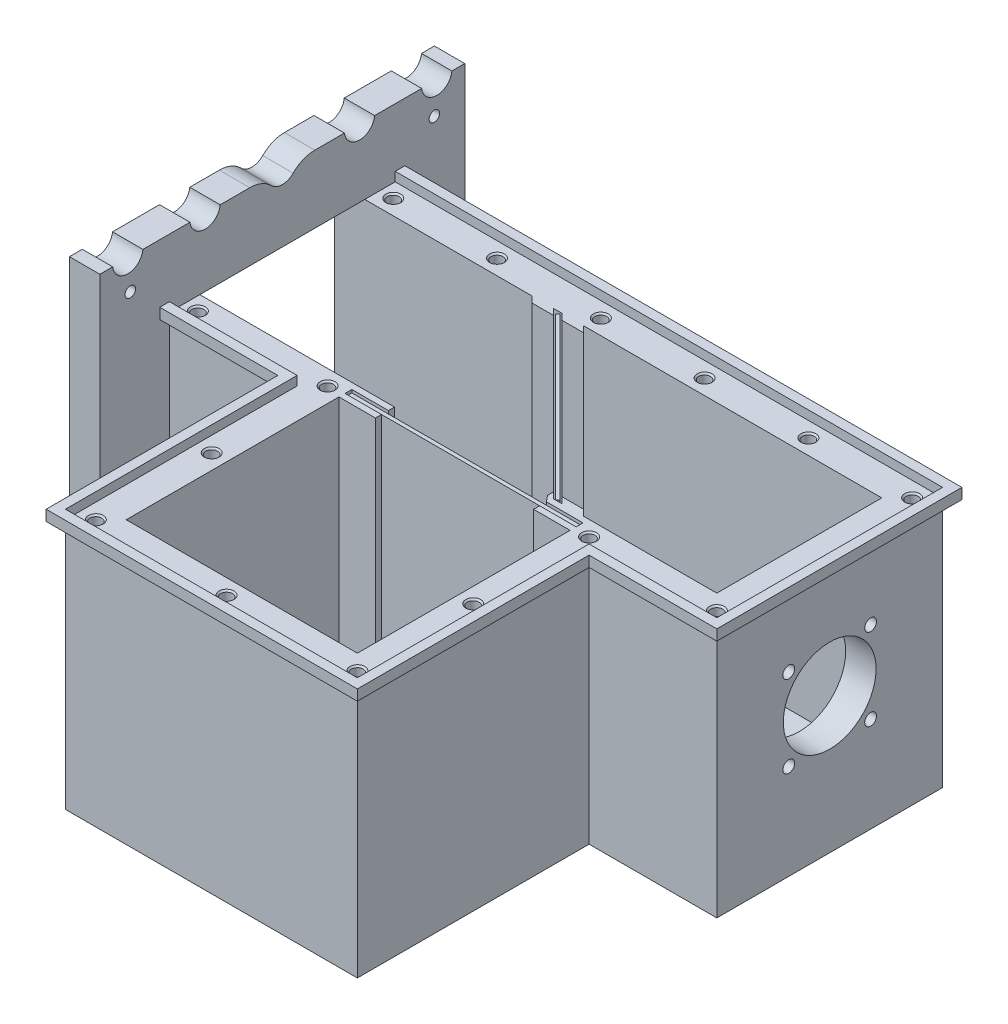
SolidWorks part; units mm, degrees
note: The reader was unsure of these and kept them because the rebuilt part matched: shared geometry of "Sketch1<5>", "Sketch1<6>", "Outline Sketch<10>".
ref_plane "Front Plane" through (0, 0, 0) normal (0, 0, 1) x (1, 0, 0)
ref_plane "Top Plane" through (0, 0, 0) normal (0, 1, 0) x (1, 0, 0)
ref_plane "Right Plane" through (0, 0, 0) normal (1, 0, 0) x (0, 0, -1)
sketch "Outline Sketch" plane through (0, 0, 0) normal (0, 1, 0) x (1, 0, 0)
  line L0 (78.4332, -3.5355) -> (81.9688, 0)
  line L1 (0, 0) -> (180, 0)
  line L2 (0, 0) -> (0, -54.2401)
  line L3 (0, -54.2401) -> (180, -54.2401)
  line L4 (180, 0) -> (180, -54.2401)
  line L9 (81.9688, 0) -> (132.6734, -50.7046)
  line L10 (132.6734, -50.7046) -> (129.1378, -54.2401)
  line L11 (129.1378, -54.2401) -> (78.4332, -3.5355)
  line L12 (72.0693, 0) -> (68.5337, -3.5355)
  line L13 (68.5337, -3.5355) -> (119.2383, -54.2401)
  line L14 (119.2383, -54.2401) -> (122.7739, -50.7046)
  line L15 (122.7739, -50.7046) -> (72.0693, 0)
  line L16 (0, 10.3799) -> (0, -64.6201) construction
  line L17 (73.4835, -0.7071) -> (126.5165, -53.7401) construction
  line L18 (126.5165, -53.7401) -> (127.2236, -53.033) construction
  line L19 (127.2236, -53.033) -> (74.1906, 0) construction
  line L20 (74.1906, 0) -> (73.4835, -0.7071) construction
  line L21 (78.0797, -3.8891) -> (78.4332, -3.5355) construction
  line L22 (77.3726, -4.5962) -> (77.019, -4.9497) construction
  line L23 (100, -27.2236) -> (100, -54.2401) construction
  line L24 (62, -54.2401) -> (138, -54.2401)
  line L25 (62, -54.2401) -> (62, -130.4401)
  line L26 (62, -130.4401) -> (138, -130.4401)
  line L27 (138, -54.2401) -> (138, -130.4401)
  line L36 (62, -58.4901) -> (74, -58.4901)
  line L37 (62, -58.4901) -> (62, -60.4901)
  line L38 (62, -60.4901) -> (74, -60.4901)
  line L39 (74, -58.4901) -> (74, -60.4901)
  line L40 (138, -58.4901) -> (126, -58.4901)
  line L41 (138, -58.4901) -> (138, -60.4901)
  line L42 (138, -60.4901) -> (126, -60.4901)
  line L43 (126, -58.4901) -> (126, -60.4901)
  line L48 (137.5, -56.2401) -> (137.5, -56.7401) construction
  line L49 (62.5, -56.7401) -> (137.5, -56.7401) construction
  line L50 (62.5, -56.7401) -> (62.5, -57.9901) construction
  line L51 (62.5, -57.9901) -> (137.5, -57.9901) construction
  line L52 (137.5, -56.7401) -> (137.5, -57.9901) construction
  line L53 (137.5, -57.9901) -> (137.5, -58.4901) construction
  line L54 (137.5, -56.7401) -> (138, -56.7401) construction
  line L55 (62.5, -56.7401) -> (62, -56.7401) construction
  line L56 (0, 22.8799) -> (0, -77.1201) construction
  line L57 (10, 10) -> (190, 10)
  line L58 (0, 27.8799) -> (10, 27.8799)
  line L59 (0, 27.8799) -> (0, 0)
  line L60 (0, 0) -> (10, 0)
  line L61 (10, 27.8799) -> (10, 0)
  line L62 (0, -54.2401) -> (10, -54.2401)
  line L63 (0, -54.2401) -> (0, -82.1201)
  line L64 (0, -82.1201) -> (10, -82.1201)
  line L65 (10, -54.2401) -> (10, -82.1201)
  line L66 (190, 10) -> (190, -64.2401)
  line L67 (190, -64.2401) -> (148, -64.2401)
  line L68 (148, -64.2401) -> (148, -140.4401)
  line L69 (148, -140.4401) -> (52, -140.4401)
  line L70 (52, -140.4401) -> (52, -64.2401)
  line L71 (52, -64.2401) -> (10, -64.2401)
  line L72 (180, 0) -> (180, 10) construction
  line L73 (180, 0) -> (190, 0) construction
  line L74 (148, -64.2401) -> (148, -54.2401) construction
  line L75 (138, -130.4401) -> (148, -130.4401) construction
  line L76 (62, -130.4401) -> (62, -140.4401) construction
  line L77 (62, -130.4401) -> (52, -130.4401) construction
  line L78 (52, -64.2401) -> (52, -54.2401) construction
  line L79 (68.5337, -3.5355) -> (68.5337, 0)
  line L80 (126.5165, -53.7401) -> (127.5772, -52.6795)
  line L81 (10, 0) -> (10, -54.2401)
  line L82 (10, 5) -> (190, 5) construction
  line L83 (185, 10) -> (185, -64.2401) construction
  line L84 (190, -59.2401) -> (138, -59.2401) construction
  line L85 (10, -59.2401) -> (62, -59.2401) construction
  line L86 (57, -54.2401) -> (57, -140.4401) construction
  line L87 (52, -135.4401) -> (148, -135.4401) construction
  line L88 (143, -54.2401) -> (143, -140.4401) construction
  line L89 (68.5337, -3.5355) -> (64.9982, 0)
  line L90 (190, -11.8701) -> (200, -11.8701) construction
  line L91 (190, -11.8701) -> (190, -42.3701) construction
  line L92 (190, -42.3701) -> (200, -42.3701) construction
  line L93 (200, -11.8701) -> (200, -42.3701) construction
  line L94 (78.4332, -3.5355) -> (74.8977, 0)
  line L95 (74.8977, 0) -> (81.9688, 0)
  line L96 (74.0693, -2) -> (66.9982, -2)
  line L97 (76.8977, -2) -> (83.9688, -2)
  line L98 (132.6734, -50.7046) -> (136.2089, -54.2401)
  line L99 (127.1378, -52.2401) -> (134.2089, -52.2401)
  line L100 (122.7739, -50.7046) -> (126.3094, -54.2401)
  line L101 (126.3094, -54.2401) -> (119.2383, -54.2401)
  line L102 (124.3094, -52.2401) -> (117.2383, -52.2401)
  line L103 (100, -54.2401) -> (100, -57.9901) construction
  line L104 (62, -54.2401) -> (74, -54.2401)
  line L105 (62, -54.2401) -> (62, -56.2401)
  line L106 (62, -56.2401) -> (74, -56.2401)
  line L107 (74, -54.2401) -> (74, -56.2401)
  line L108 (138, -54.2401) -> (126, -54.2401)
  line L109 (138, -54.2401) -> (138, -56.2401)
  line L110 (138, -56.2401) -> (126, -56.2401)
  line L111 (126, -54.2401) -> (126, -56.2401)
  line L112 (124.3094, -52.2401) -> (124.3094, -54.2401)
  line L113 (124.3094, -54.2401) -> (126.3094, -54.2401)
  line L114 (124.3094, -54.2401) -> (126, -56.2401)
  line L115 (180, -54.2401) -> (180, -64.2401) construction
  point P18 (0, -27.1201)
  point P51 (0, -27.1201)
  point P52 (0, -27.1201)
  point P80 (180, 5)
  point P83 (185, 0)
  point P85 (200, -27.1201)
  point P86 (190, -27.1201)
  point P94 (148, -59.2401)
  point P103 (57, -130.4401)
  point P104 (143, -130.4401)
  point P105 (62, -135.4401)
  dimension "D23" = 10
  dimension "D24" = 30.5
  dimension "D25" = 2
  dimension "D26" = 2
  dimension "D1" = 5
  dimension "D2" = 45
  dimension "D3" = 1
  dimension "D4" = 75
  dimension "D5" = 200
  dimension "D6" = 53.7401
  dimension "D7" = 0.5
  dimension "D8" = 75
  dimension "D9" = 1.25
  dimension "D10" = 0.5
  dimension "D11" = 76
  dimension "D12" = 52.3259
  dimension "D13" = 0.5
  dimension "D14" = 2
  dimension "D15" = 100
  dimension "D16" = 76.2
  dimension "D17" = 75
  dimension "D18" = 100
  dimension "D19" = 10
  dimension "D20" = 5
  dimension "D21" = 10
  dimension "D22" = 17.8799
  dimension "D27" = 52
  dimension "D29" = 0.5
extrude "Floor" add sketch "Outline Sketch" along normal blind 7
extrude "Walls" add sketch "Sketch1<5>" along normal blind 75.5 from surface at 7
sketch "Sketch1<5>" plane through (0, 0, 0) normal (0, 1, 0) x (1, 0, 0) same geometry as "Outline Sketch"
extrude "Beam Splitter Supports" add sketch "Sketch1<6>" along normal blind 2 from surface at 7 separate body contours L11 L99 L10 L9 L97 L0 | L99 L10 L3 L98 | L10 L99 L98 | L99 L11 L10 | L102 L14 L15 L96 L12 L13 | L14 L102 L13 | L112 L102 L14 L3 | L102 L100 L14 | L100 L112 L101 | L94 L97 L0 L1 | L0 L97 L9 | L97 L94 L0 | L96 L79 L1 L89 | L79 L96 L89 | L12 L96 L79 | L96 L15 L12 | L96 L12 L1 L79 starting at face at (90, 7, 56.0437)
sketch "Sketch1<6>" plane through (0, 0, 0) normal (0, 1, 0) x (1, 0, 0) same geometry as "Outline Sketch"
extrude "Beam Splitter Vertical Supports" add sketch "Outline Sketch<10>" along normal up to surface (82.5 mm away) contours L96 L15 L12 | L96 L12 L1 L79 | L96 L79 L1 L89 | L94 L97 L0 L1 | L0 L97 L9 | L99 L11 L10 | L99 L10 L3 L98 | L100 L112 L101 | L101 L114 L111 up to face at (99.2857, 82.5, 60.5915)
sketch "Outline Sketch<10>" plane through (0, 0, 0) normal (0, 1, 0) x (1, 0, 0) same geometry as "Outline Sketch"
ref_plane "SM1 Camera Flange Plane" through (190, 0, 0) normal (1, 0, 0) x (0, 0, -1)
sketch "SM1 Flange Sketch" plane through (190, 0, 0) normal (1, 0, 0) x (0, 0, -1)
  line L0 (-54.2401, 82.5) -> (0, 82.5) construction
  line L1 (-40.5821, 58.212) -> (-13.6581, 58.212) construction
  line L2 (-40.5821, 58.212) -> (-40.5821, 31.288) construction
  line L3 (-40.5821, 31.288) -> (-13.6581, 31.288) construction
  line L4 (-13.6581, 58.212) -> (-13.6581, 31.288) construction
  line L6 (-64.2401, 9) -> (10, 9) construction
  line L7 (-64.2401, 82.5) -> (-64.2401, 0) construction
  line L8 (10, 82.5) -> (10, 0) construction
  line L10 (22.8799, 0) -> (-77.1201, 0) construction
  line L11 (-64.2401, 82.5) -> (10, 82.5) construction
  line L12 (-64.2401, 7) -> (10, 7) construction
  line L14 (-64.2401, 82.5) -> (-64.2401, 0) construction
  line L15 (-64.2401, 82) -> (10, 82) construction
  line L16 (10, 80.5) -> (-64.2401, 80.5) construction
  circle A0 centre (-27.1201, 44.75) radius 15.25
  circle A1 centre (-40.5821, 58.212) radius 1.945
  circle A2 centre (-13.6581, 58.212) radius 1.945
  circle A3 centre (-13.6581, 31.288) radius 1.945
  circle A4 centre (-40.5821, 31.288) radius 1.945
  point P13 (-27.1201, 58.212)
  point P14 (-13.6581, 44.75)
  point P17 (-27.1201, 82.5)
  dimension "D2" = 30.5
  dimension "D1" = 26.924
  dimension "D7" = 75
  dimension "D4" = 35.75
extrude "SM1 Flange Cutout" cut sketch "SM1 Flange Sketch" against normal up to surface (10 mm away) up to face at (180, 44.75, 27.1201)
sketch "BS & Diffuser Example Sketch" plane through (0, 0, 0) normal (0, 1, 0) x (1, 0, 0)
  line L0 (73.4835, -0.7071) -> (126.5165, -53.7401)
  line L1 (126.5165, -53.7401) -> (127.2236, -53.033)
  line L2 (127.2236, -53.033) -> (74.1906, 0)
  line L3 (74.1906, 0) -> (73.4835, -0.7071)
  line L4 (62.5, -56.7401) -> (62.5, -57.9901)
  line L5 (62.5, -57.9901) -> (137.5, -57.9901)
  line L6 (137.5, -57.9901) -> (137.5, -56.7401)
  line L7 (137.5, -56.7401) -> (62.5, -56.7401)
extrude "BS & Diffuser Example Planes" add sketch "BS & Diffuser Example Sketch" along normal blind 75 from surface at 7 separate body contours L6 L7 L4 L5 | L2 L3 L0 L1 starting at face at (81.9339, 7, 56.0437)
ref_plane "Cryostat Flange Plane" through (10, 0, 0) normal (-1, 0, 0) x (0, 0, 1)
sketch "Cryostat Flange Sketch" plane through (10, 0, 0) normal (-1, 0, 0) x (0, 0, 1)
  line L0 (-23.6799, 105.2669) -> (1.7201, 105.2669) construction
  line L1 (-32.8799, 104.75) -> (87.1201, 104.75)
  line L2 (-32.8799, 104.75) -> (-32.8799, -15.25)
  line L3 (-32.8799, -15.25) -> (87.1201, -15.25)
  line L4 (87.1201, 104.75) -> (87.1201, -15.25)
  line L5 (-22.8799, 94.75) -> (77.1201, 94.75) construction
  line L6 (-22.8799, 94.75) -> (-22.8799, -5.25) construction
  line L7 (-22.8799, -5.25) -> (77.1201, -5.25) construction
  line L8 (77.1201, 94.75) -> (77.1201, -5.25) construction
  line L9 (-10.3799, 82.25) -> (64.6201, 82.25) construction
  line L10 (-10.3799, 82.25) -> (-10.3799, 7.25) construction
  line L11 (-10.3799, 7.25) -> (64.6201, 7.25) construction
  line L12 (64.6201, 82.25) -> (64.6201, 7.25) construction
  line L13 (0, 7) -> (54.2401, 7)
  line L14 (0, 7) -> (0, 82.5)
  line L15 (0, 82.5) -> (54.2401, 82.5)
  line L16 (54.2401, 7) -> (54.2401, 82.5)
  line L17 (1.7201, 105.2669) -> (27.1201, 105.2669) construction
  line L18 (27.1201, 105.2669) -> (52.5201, 105.2669) construction
  line L19 (52.5201, 105.2669) -> (77.9201, 105.2669) construction
  circle A0 centre (-22.8799, 94.75) radius 1.725
  circle A1 centre (77.1201, 94.75) radius 1.725
  circle A2 centre (77.1201, -5.25) radius 1.725
  circle A3 centre (-22.8799, -5.25) radius 1.725
  circle A4 centre (27.1201, 44.75) radius 0.5 construction
  circle A5 centre (27.1201, 44.75) radius 15.25 construction
  circle A6 centre (-23.6799, 105.2669) radius 5
  circle A7 centre (1.7201, 105.2669) radius 5
  circle A8 centre (27.1201, 105.2669) radius 5
  circle A9 centre (52.5201, 105.2669) radius 5
  circle A10 centre (77.9201, 105.2669) radius 5
  point P12 (27.1201, 104.75)
  point P13 (-32.8799, 44.75)
  point P14 (27.1201, 82.25)
  point P17 (-10.3799, 44.75)
  point P42 (0, 0)
  point P43 (27.1201, 109.7584)
  point P44 (27.1201, 106.4508)
  dimension "D3" = 3.45
  dimension "D7" = 1
  dimension "D10" = 10
  dimension "D1" = 120
  dimension "D2" = 100
  dimension "D4" = 10
  dimension "D5" = 10
  dimension "D6" = 75
  dimension "D8" = 25.4
  dimension "D11" = 0.5169
extrude "Crystat Flange Extrusion " add sketch "Cryostat Flange Sketch" along normal blind 10 contours A10 L1 A9 A8 A7 A6 L2 L3 L4 A3 A2 A1 A0 L16 L13 L14 L15
ref_plane "Threaded Inserts" through (0, 82.5, 0) normal (0, 1, 0) x (1, 0, 0)
sketch "Threaded Insert Sketch" plane through (0, 82.5, 0) normal (0, 1, 0) x (1, 0, 0)
  line L0 (10, 5) -> (190, 5) construction
  line L1 (10, 27.8799) -> (10, 0) construction
  line L2 (10, -59.2401) -> (62, -59.2401) construction
  line L3 (190, -59.2401) -> (138, -59.2401) construction
  line L4 (143, -54.2401) -> (143, -140.4401) construction
  line L5 (185, 10) -> (185, -64.2401) construction
  line L6 (57, -54.2401) -> (57, -140.4401) construction
  line L7 (52, -135.4401) -> (148, -135.4401) construction
  circle A0 centre (14.3688, 5) radius 1.9431
  circle A1 centre (14.3688, 5) radius 4.3688 construction
  circle A2 centre (48.495, 5) radius 1.9431
  circle A3 centre (48.495, 5) radius 4.3688 construction
  circle A4 centre (82.6213, 5) radius 1.9431
  circle A5 centre (82.6213, 5) radius 4.3688 construction
  circle A6 centre (116.7475, 5) radius 1.9431
  circle A7 centre (116.7475, 5) radius 4.3688 construction
  circle A8 centre (150.8738, 5) radius 1.9431
  circle A9 centre (150.8738, 5) radius 4.3688 construction
  circle A10 centre (185, 5) radius 1.9431
  circle A11 centre (185, 5) radius 4.3688 construction
  circle A12 centre (14.3688, -59.2401) radius 1.9431
  circle A13 centre (14.3688, -59.2401) radius 4.3688 construction
  circle A14 centre (57, -59.2401) radius 1.9431
  circle A15 centre (57, -59.2401) radius 4.3688 construction
  circle A16 centre (185, -59.2401) radius 1.9431
  circle A17 centre (185, -59.2401) radius 4.3688 construction
  circle A18 centre (143, -59.2401) radius 1.9431
  circle A19 centre (143, -59.2401) radius 4.3688 construction
  circle A20 centre (57, -135.4401) radius 1.9431
  circle A21 centre (57, -135.4401) radius 4.3688 construction
  circle A22 centre (143, -135.4401) radius 1.9431
  circle A23 centre (143, -135.4401) radius 4.3688 construction
  circle A24 centre (57, -97.3401) radius 1.9431
  circle A25 centre (57, -97.3401) radius 4.3688 construction
  circle A26 centre (143, -97.3401) radius 1.9431
  circle A27 centre (143, -97.3401) radius 4.3688 construction
  circle A28 centre (100, -135.4401) radius 1.9431
  circle A29 centre (100, -135.4401) radius 4.3688 construction
  dimension "D1" = 3.8862
  dimension "D2" = 8.7376
  dimension "D4" = 34.1262
  dimension "D3" = 6
extrude "Cut-Extrude2" cut sketch "Threaded Insert Sketch" against normal blind 10 contours A0 | A2 | A4 | A6 | A10 | A8 | A16 | A18 | A26 | A28 | A22 | A20 | A24 | A14 | A12
chamfer "Chamfer1" distance 0.5 angle 45 15 edges at (14.3688, 82.5, -3.0569) (14.3688, 82.5, 61.1832) (57, 82.5, 137.3832) (100, 82.5, 137.3832) (143, 82.5, 137.3832) (57, 82.5, 99.2832) (57, 82.5, 61.1832) (143, 82.5, 99.2832) (143, 82.5, 61.1832) (185, 82.5, 61.1832) (185, 82.5, -3.0569) (116.7475, 82.5, -3.0569) (150.8738, 82.5, -3.0569) (82.6213, 82.5, -3.0569) (48.495, 82.5, -3.0569)
sketch "Sketch7" plane through (0, 82.5, 0) normal (0, 1, 0) x (1, 0, 0)
  line L0 (10, 13.175) -> (193.175, 13.175)
  line L1 (10, 27.8799) -> (10, 0) construction
  line L2 (193.175, 13.175) -> (193.175, -67.4151)
  line L3 (193.175, -67.4151) -> (151.175, -67.4151)
  line L4 (151.175, -67.4151) -> (151.175, -143.6151)
  line L5 (151.175, -143.6151) -> (48.825, -143.6151)
  line L6 (48.825, -143.6151) -> (48.825, -67.4151)
  line L7 (48.825, -67.4151) -> (10, -67.4151)
  line L9 (10, -54.2401) -> (10, -82.1201) construction
  line L10 (190, 10) -> (190, 13.175) construction
  line L11 (190, -81.8967) -> (190, 81.8967) construction
  line L12 (190, 10) -> (193.175, 10) construction
  line L13 (190, -64.2401) -> (193.175, -64.2401) construction
  line L14 (190, -64.2401) -> (190, -67.4151) construction
  line L15 (151.175, -67.4151) -> (151.175, -64.2401) construction
  line L16 (190, -64.2401) -> (148, -64.2401) construction
  line L17 (151.175, -67.4151) -> (148, -67.4151) construction
  line L18 (148, -64.2401) -> (148, -140.4401) construction
  line L19 (148, -140.4401) -> (151.175, -140.4401) construction
  line L20 (148, -140.4401) -> (148, -143.6151) construction
  line L21 (52, -140.4401) -> (52, -143.6151) construction
  line L22 (52, -140.4401) -> (48.825, -140.4401) construction
  line L23 (48.825, -67.4151) -> (48.825, -64.2401) construction
  line L24 (52, -64.2401) -> (10, -64.2401) construction
  line L25 (48.825, -67.4151) -> (52, -67.4151) construction
  line L26 (52, -140.4401) -> (52, -64.2401) construction
  line L27 (10, 10) -> (190, 10) construction
  line L28 (10, 10) -> (190, 10)
  line L29 (190, 10) -> (190, -64.2401)
  line L30 (190, -64.2401) -> (148, -64.2401)
  line L31 (148, -64.2401) -> (148, -140.4401)
  line L32 (148, -140.4401) -> (52, -140.4401)
  line L33 (52, -140.4401) -> (52, -64.2401)
  line L34 (52, -64.2401) -> (10, -64.2401)
  line L35 (10, 13.175) -> (10, 10)
  line L36 (10, -64.2401) -> (10, -67.4151)
  dimension "D1" = 3.175
extrude "Boss-Extrude12" add sketch "Sketch7" along normal blind 3 and the other way blind 3 separate body
chamfer "Chamfer3" distance 2.5 angle 45 7 edges at (101.5875, 79.5, -13.175) (193.175, 79.5, 27.1201) (172.175, 79.5, 67.4151) (151.175, 79.5, 105.5151) (100, 79.5, 143.6151) (48.825, 79.5, 105.5151) (29.4125, 79.5, 67.4151)
sketch "Sketch6" [suppressed] plane through (10, 0, 0) normal (-1, 0, 0) x (0, 0, 1)
  line L0 (63.7401, 79.5) -> (139.9401, 79.5) construction
  line L1 (-10, 86.5) -> (63.7401, 86.5)
  line L2 (-10, 86.5) -> (-10, 79.5)
  line L3 (-10, 79.5) -> (63.7401, 79.5)
  line L4 (63.7401, 86.5) -> (63.7401, 79.5)
  dimension "D1" = 7
extrude "Cut-Extrude3" [suppressed] cut sketch "Sketch6" along normal blind 3
chamfer "Chamfer2" [suppressed] distance 1 angle 45
sketch "Sketch8" plane through (0, 0, 0) normal (0, -1, 0) x (1, 0, 0)
  line L0 (148, 140.4401) -> (52, 140.4401) construction
  line L2 (193.175, 67.4151) -> (193.175, -13.175) construction
  circle A0 centre (133.175, 27.1201) radius 4.0767
  circle A1 centre (100, 102.9401) radius 4.0767
  circle A2 centre (73.175, 27.1201) radius 4.0767
  point P8 (100, 140.4401)
  point P11 (193.175, 27.1201)
  dimension "D1" = 8.1534
  dimension "D2" = 37.5
  dimension "D3" = 60
  dimension "D4" = 60
extrude "1/4-20 Support Leg Holes" cut sketch "Sketch8" against normal blind 6.35
fillet "Fillet1" radius 10 2 edges at (5, 104.75, 22.1468) (5, 104.75, 32.0933)
equation "\"Peg_height\"=2"
equation "\"D1@Beam Splitter Supports\"=\"Peg_height\""
equation "\"BS_Height\"=75"
equation "\"D1@BS & Diffuser Example Planes\"=\"BS_Height\""
equation "\"Floor_thickness\" = 7"
equation "\"D1@Floor\"=\"Floor_thickness\""
equation "\"D5@SM1 Flange Sketch\"=\"Floor_thickness\"+\"Peg_height\""
equation "\"D6@SM1 Flange Sketch\"=\"Floor_thickness\""
equation "\"D7@SM1 Flange Sketch\"=\"BS_Height\""
equation "\"D4@SM1 Flange Sketch\"=(\"D8@SM1 Flange Sketch\"/2)"
equation "\"D9@SM1 Flange Sketch\"=\"Peg_height\""
equation "\"D4@Cryostat Flange Sketch\"=(\"D1@Cryostat Flange Sketch\"-\"D2@Cryostat Flange Sketch\")/2"
equation "\"D5@Cryostat Flange Sketch\"=\"D4@Cryostat Flange Sketch\""
equation "\"D4@Threaded Insert Sketch\"=((180-8.74))/5 - (0.6288/5)"
